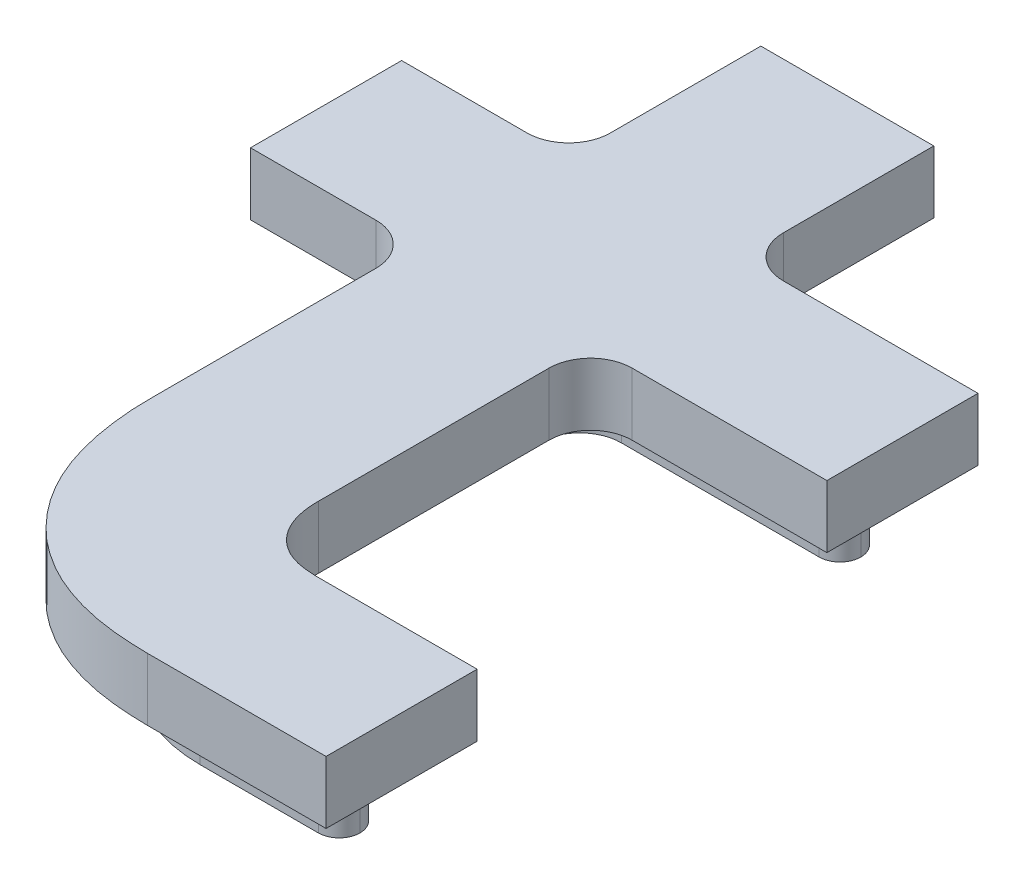
SolidWorks part; units mm, degrees
material "Сосна"
ref_plane "Спереди" through (0, 0, 0) normal (0, 0, 1) x (1, 0, 0)
ref_plane "Сверху" through (0, 0, 0) normal (0, 1, 0) x (1, 0, 0)
ref_plane "Справа" through (0, 0, 0) normal (1, 0, 0) x (0, 0, -1)
sketch "Эскиз t" plane through (0, 0, 0) normal (0, 1, 0) x (1, 0, 0)
  line L0 (0, 153.8462) -> (40.1397, 153.8462)
  line L1 (40.1397, 153.8462) -> (40.1397, 200)
  line L2 (40.1397, 200) -> (81.6862, 200)
  line L3 (81.6862, 200) -> (81.6862, 153.8462)
  line L4 (81.6862, 153.8462) -> (138.4571, 153.8462)
  line L5 (138.4571, 153.8462) -> (138.4571, 117.5481)
  line L6 (138.4571, 117.5481) -> (81.6862, 117.5481)
  line L7 (81.6862, 117.5481) -> (81.6862, 52.2436)
  line L8 (96.9106, 36.2981) -> (135.6926, 36.2981)
  line L9 (135.6926, 36.2981) -> (135.6926, 0)
  line L10 (135.6926, 0) -> (92.7439, 0)
  line L11 (40.1397, 53.8061) -> (40.1397, 117.5481)
  line L12 (40.1397, 117.5481) -> (0, 117.5481)
  line L13 (0, 117.5481) -> (0, 153.8462)
  line L14 (0, -40.814) -> (0, 222.1621) construction
  line L15 (-87.9774, 0) -> (197.2997, 0) construction
  spline S0 degree 3 poles (81.6862, 52.2436) (81.6553, 49.9829) (82.0854, 46.6905) (83.8177, 42.7933) (85.6039, 40.4398) (87.8479, 38.5612) (91.5433, 36.6867) (94.7583, 36.3504) (96.9106, 36.2981) knots 0 0 0 0 0.271489 0.391201 0.507819 0.622674 0.739445 1 1 1 1
  spline S1 degree 3 poles (92.7439, 0) (88.8492, 0.0503) (83.1165, 0.3658) (75.8105, 1.8985) (70.7972, 3.4788) (66.0841, 5.4542) (61.7495, 7.9819) (57.6914, 10.8559) (54.0534, 14.2541) (50.7675, 18.0064) (47.9085, 22.1198) (45.4837, 26.563) (43.5199, 31.3617) (42.0023, 36.5049) (40.5498, 43.9894) (40.0847, 49.8218) (40.1397, 53.8061) knots 0 0 0 0 0.137099 0.200908 0.261935 0.321669 0.380134 0.437984 0.496125 0.554688 0.613033 0.671859 0.732277 0.794963 0.860058 1 1 1 1
  dimension "D1" = 40.1397
  dimension "D2" = 40.1397
  dimension "D3" = 41.5465
  dimension "D4" = 41.5465
  dimension "D5" = 117.5481
  dimension "D6" = 36.2981
  dimension "D7" = 117.5481
  dimension "D8" = 36.2981
  dimension "D9" = 138.4571
  dimension "D10" = 200
  dimension "D11" = 36.2981
  dimension "D12" = 135.6926
extrude "t" add sketch "Эскиз t" along normal blind 15
sketch "Эскиз крепежа подсветки" plane through (0, 0, 0) normal (0, 1, 0) x (1, 0, 0)
  line L0 (60.9132, 190) -> (60.9132, 49.5113)
  line L1 (92.2755, 18.149) -> (125.6971, 18.149)
  line L2 (10, 135.699) -> (128.4571, 135.699)
  arc A0 (60.9132, 49.5113) -> (92.2755, 18.149) centre (92.2755, 49.5113) ccw
  dimension "D1" = 60.9132
  dimension "D2" = 18.149
  dimension "D3" = 135.699
  dimension "D4" = 190
  dimension "D5" = 10
  dimension "D6" = 128.4571
  dimension "D7" = 125.6971
extrude "Вытянуть-Тонкостенный1" add sketch "Эскиз крепежа подсветки" against normal blind 15 thin thin type mid plane wall 10
fillet "Внешнее скругление под ленту" radius 5 8 edges at (128.4571, -7.5, -140.699) (128.4571, -7.5, -130.699) (125.6971, -7.5, -23.149) (125.6971, -7.5, -13.149) (10, -7.5, -130.699) (10, -7.5, -140.699) (55.9132, -7.5, -190) (65.9132, -7.5, -190)
fillet "Внутренне скругление под ленту" radius 10 4 edges at (65.9132, -7.5, -130.699) (55.9132, -7.5, -130.699) (55.9132, -7.5, -140.699) (65.9132, -7.5, -140.699)
fillet "Скругление под фрезу" radius 10 4 edges at (40.1397, 7.5, -117.5481) (81.6862, 7.5, -117.5481) (81.6862, 7.5, -153.8462) (40.1397, 7.5, -153.8462)
sketch "Эскиз разметки под шурупы" plane through (0, 0, 0) normal (0, 1, 0) x (1, 0, 0)
  circle A0 centre (60.9132, 135.699) radius 1.5
  circle A1 centre (120.6971, 18.149) radius 1.5
  circle A2 centre (123.4571, 135.699) radius 1.5
  point P7 (0, 0)
  dimension "D1" = 3
  dimension "D2" = 3
  dimension "D7" = 3
  dimension "D5" = 18.149
  dimension "D6" = 120.6971
  dimension "D8" = 2.76
  dimension "D4" = 117.55
  dimension "D3" = 59.7838
extrude "Разметка под шурупы" cut sketch "Эскиз разметки под шурупы" against normal through all
equation "\"drill\"= 3мм"
equation "\"D1@Эскиз разметки под шурупы\" = \"drill\""
equation "\"D2@Эскиз разметки под шурупы\" = \"drill\""
equation "\"D7@Эскиз разметки под шурупы\"=\"drill\""
